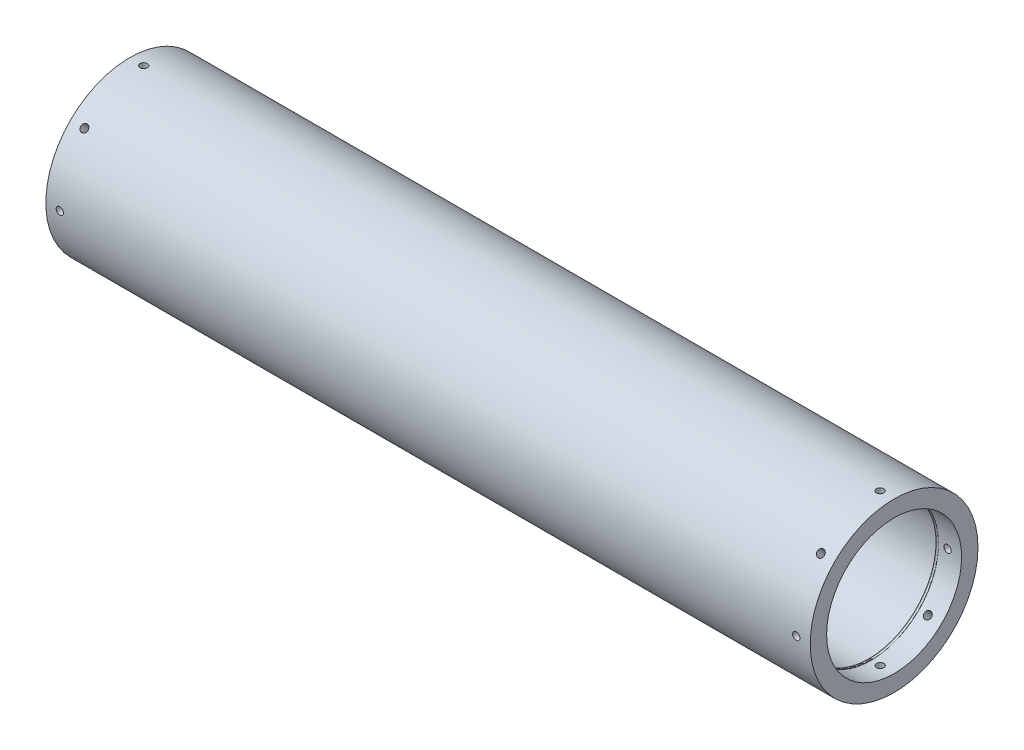
SolidWorks part; units mm, degrees
material "7075-T6 (SN)"
ref_plane "Front Plane" through (0, 0, 0) normal (0, 0, 1) x (1, 0, 0)
ref_plane "Top Plane" through (0, 0, 0) normal (0, 1, 0) x (1, 0, 0)
ref_plane "Right Plane" through (0, 0, 0) normal (1, 0, 0) x (0, 0, -1)
sketch "Sketch1" plane through (0, 0, 0) normal (1, 0, 0) x (0, 0, -1)
  circle A0 centre (0, 0) radius 45.974
  circle A1 centre (0, 0) radius 57.15
  dimension "D1" = 91.948
  dimension "D2" = 114.3
extrude "Boss-Extrude1" add sketch "Sketch1" along normal blind 520.7
sketch "Sketch2" plane through (0, 0, 0) normal (-1, 0, 0) x (0, 0, 1)
  circle A0 centre (0, 0) radius 44.577
  circle A2 centre (0, 0) radius 53.975
  dimension "D1" = 89.154
  dimension "D2" = 107.95
extrude "Boss-Extrude2" add sketch "Sketch2" against normal blind 95.25
ref_plane "Plane1" through (0, 0, 57.15) normal (0, 0, 1) x (1, 0, 0)
sketch "Sketch4" plane through (0, 0, 57.15) normal (0, 0, 1) x (1, 0, 0)
  circle A0 centre (9.525, 0) radius 2.4892
  dimension "D2" = 4.9784
  dimension "D1" = 9.525
extrude "Cut-Extrude1" cut sketch "Sketch4" against normal blind 19.05
pattern_circular "CirPattern1" count 8 every 45 about axis through (520.7, 0, 0) along (-1, 0, 0) of "Cut-Extrude1" reverse direction yes
sketch "Sketch5" plane through (0, 0, 57.15) normal (0, 0, 1) x (1, 0, 0)
  line L0 (520.7, -57.15) -> (520.7, 57.15) construction
  circle A0 centre (511.175, 0) radius 2.4892
  dimension "D2" = 4.9784
  dimension "D1" = 9.525
extrude "Cut-Extrude2" cut sketch "Sketch5" against normal blind 19.05
pattern_circular "CirPattern2" count 8 every 45 about axis through (520.7, 0, 0) along (-1, 0, 0) of "Cut-Extrude2"
sketch "Sketch6" plane through (0, 0, 0) normal (0, 0, 1) x (1, 0, 0)
  line L0 (520.7, -57.15) -> (520.7, 57.15) construction
  line L1 (0, 0) -> (569.0333, 0) construction
  circle A0 centre (504.19, 45.72) radius 0.889
  dimension "D2" = 1.778
  dimension "D3" = 16.51
  dimension "D1" = 45.72
revolve "Cut-Revolve2" cut sketch "Sketch6" angle 360 about L1
